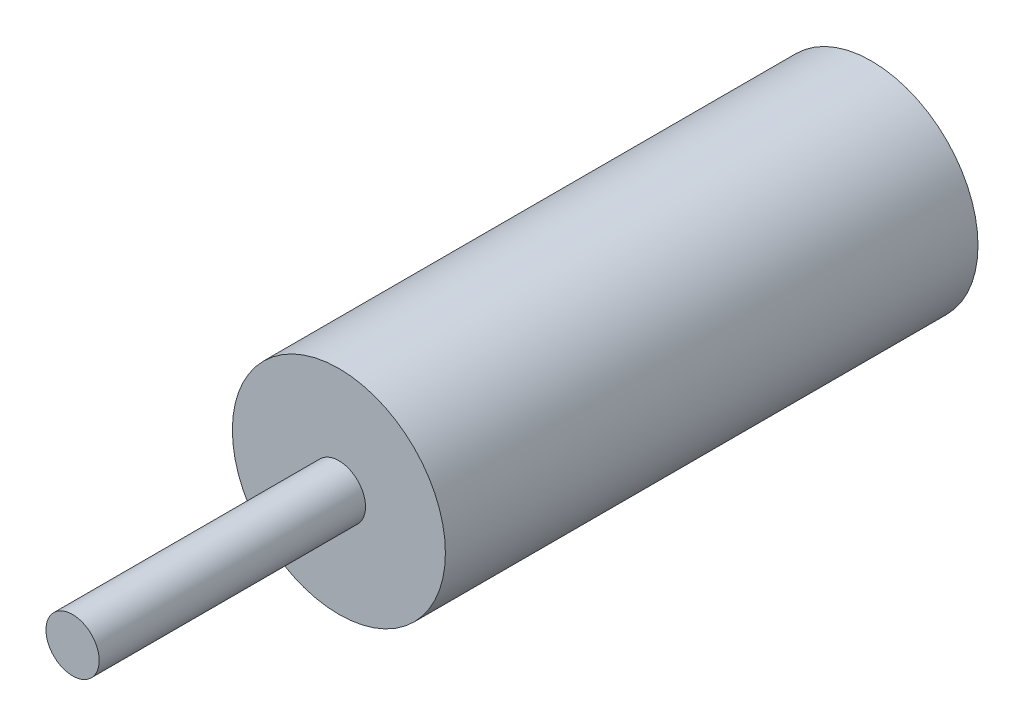
SolidWorks part; units mm, degrees
ref_plane "Front Plane" through (0, 0, 0) normal (0, 0, 1) x (1, 0, 0)
ref_plane "Top Plane" through (0, 0, 0) normal (0, 1, 0) x (1, 0, 0)
ref_plane "Right Plane" through (0, 0, 0) normal (1, 0, 0) x (0, 0, -1)
sketch "Sketch1" plane through (0, 0, 0) normal (0, 0, 1) x (1, 0, 0)
  circle A0 centre (0, 0) radius 4
  circle A1 centre (0, 0) radius 1
  dimension "D1" = 2
  dimension "D2" = 8
extrude "Boss-Extrude1" add sketch "Sketch1" along normal blind 20 contours A0 A1 | A1 region at (-3.8869, 0, 0) region at (0, 0, 0)
extrude "Boss-Extrude2" add sketch "Sketch1<3>" along normal blind 30 contours A1 region at (0, 0, 0)
sketch "Sketch1<3>" plane through (0, 0, 0) normal (0, 0, 1) x (1, 0, 0) same geometry as "Sketch1"
